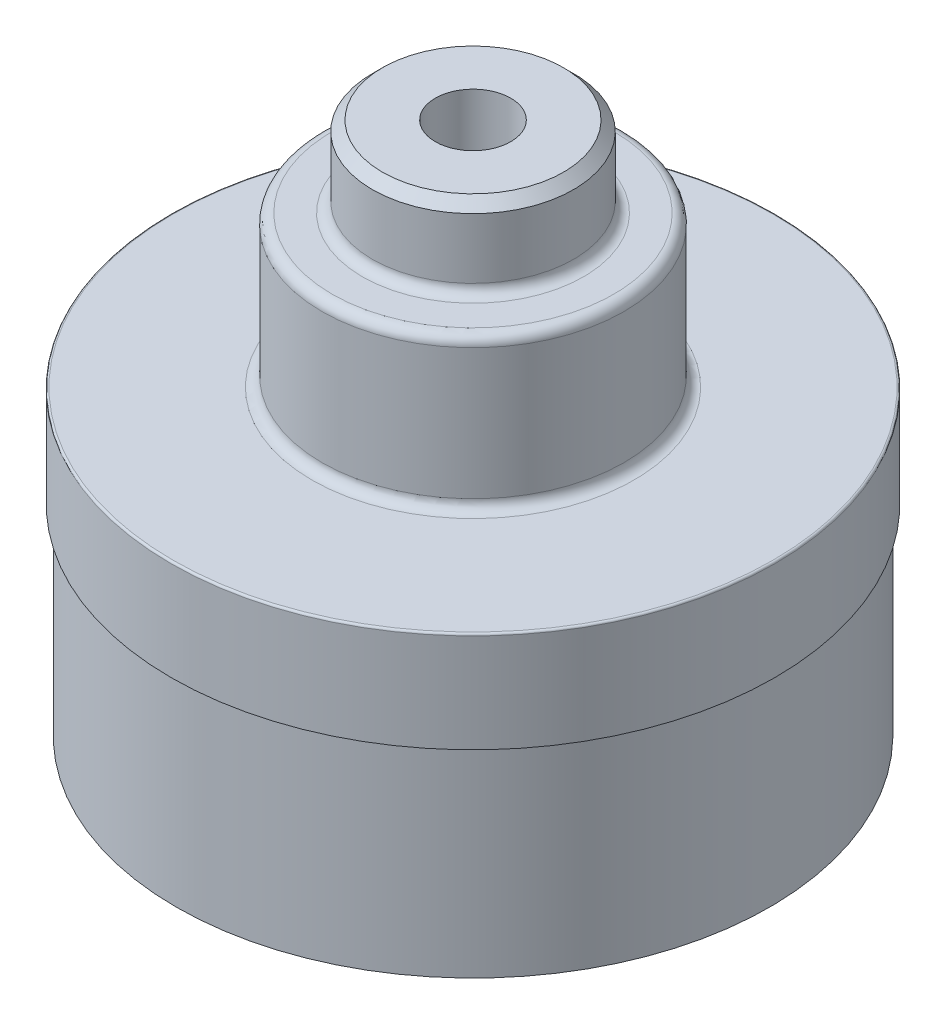
SolidWorks part; units mm, degrees
material "1060 Alloy"
ref_plane "Front Plane" through (0, 0, 0) normal (0, 0, 1) x (1, 0, 0)
ref_plane "Top Plane" through (0, 0, 0) normal (0, 1, 0) x (1, 0, 0)
ref_plane "Right Plane" through (0, 0, 0) normal (1, 0, 0) x (0, 0, -1)
sketch "Sketch1" plane through (0, 0, 0) normal (0, 1, 0) x (1, 0, 0)
  circle A0 centre (0, 0) radius 37.465
  dimension "D1" = 74.93
extrude "Boss-Extrude1" add sketch "Sketch1" along normal blind 25.4
sketch "Sketch2" plane through (0, 25.4, 0) normal (0, 1, 0) x (1, 0, 0)
  circle A0 centre (0, 0) radius 38.1
  dimension "D1" = 76.2
extrude "Boss-Extrude2" add sketch "Sketch2" along normal blind 12.7
sketch "Sketch3" plane through (0, 38.1, 0) normal (0, 1, 0) x (1, 0, 0)
  circle A0 centre (0, 0) radius 19.05
  dimension "D1" = 38.1
extrude "Boss-Extrude3" add sketch "Sketch3" along normal blind 19.05
sketch "Sketch4" plane through (0, 57.15, 0) normal (0, 1, 0) x (1, 0, 0)
  circle A0 centre (0, 0) radius 12.7
  dimension "D1" = 25.4
extrude "Boss-Extrude4" add sketch "Sketch4" along normal blind 10.16
fillet "Fillet1" radius 1.27 1 edges at (0, 67.31, 12.7) profile chamfer
fillet "Fillet2" radius 1.27 1 edges at (0, 57.15, 19.05)
fillet "Fillet3" radius 0.254 1 edges at (0, 38.1, 38.1)
fillet "Fillet4" radius 1.27 1 edges at (0, 38.1, 19.05)
fillet "Fillet5" radius 1.27 1 edges at (0, 57.15, 12.7)
hole_wizard "3/8 (0.375) Diameter Hole1" positions "Sketch5" profile "Sketch7" hole size "3/8" standard "ANSI Inch"
sketch "Sketch5" plane through (0, 67.31, 0) normal (0, 1, 0) x (1, 0, 0)
  point P0 (0, 0)
sketch "Sketch7" plane through (0, 67.31, 0) normal (1, 0, 0) x (0, 0, 1)
  line L0 (0, 0) -> (0, 28.2616)
  line L1 (0, 28.2616) -> (4.7625, 25.4)
  line L2 (4.7625, 25.4) -> (4.7625, 0)
  line L5 (4.7625, 0) -> (0, 0)
  line L10 (0, 28.2616) -> (-4.7625, 25.4) construction
  line L11 (0, -6.35) -> (0, 107.95) construction
  dimension "Hole Dia." = 9.525
  dimension "Hole Depth" = 25.4
  dimension "Drill Angle" = 118
